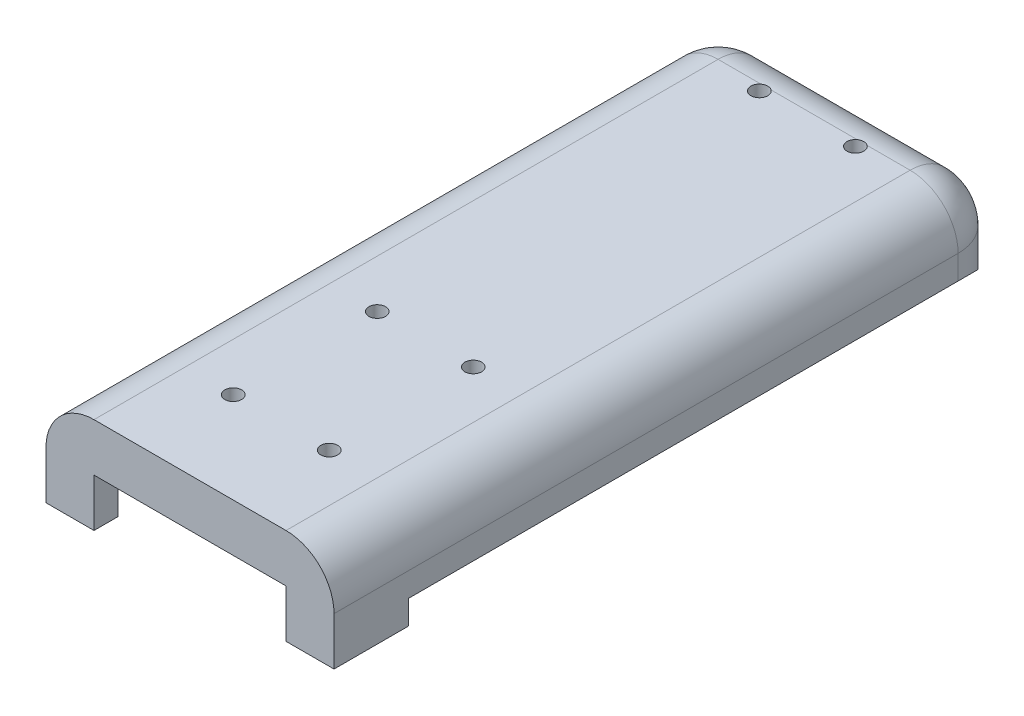
SolidWorks part; units mm, degrees
ref_plane "Front Plane" through (0, 0, 0) normal (0, 0, 1) x (1, 0, 0)
ref_plane "Top Plane" through (0, 0, 0) normal (0, 1, 0) x (1, 0, 0)
ref_plane "Right Plane" through (0, 0, 0) normal (1, 0, 0) x (0, 0, -1)
sketch "Sketch1" plane through (0, 0, 0) normal (0, 0, 1) x (1, 0, 0)
  line L1 (15, -5) -> (45, -5)
  line L3 (10, 0) -> (50, 0)
  line L7 (0, -10) -> (0, -15)
  line L11 (55, -20) -> (60, -15)
  line L12 (0, -15) -> (5, -20)
  line L13 (5, -15) -> (5, -20)
  line L14 (55, -20) -> (55, -15)
  line L16 (60, -15) -> (60, -10)
  arc A0 (10, 0) -> (0, -10) centre (10, -10) ccw
  arc A1 (50, 0) -> (60, -10) centre (50, -10) cw
  arc A2 (55, -15) -> (45, -5) centre (45, -15) ccw
  arc A3 (5, -15) -> (15, -5) centre (15, -15) cw
  point P7 (0, 0)
  point P12 (60, 0)
  point P17 (55, -5)
  point P21 (5, -5)
  dimension "D9" = 10
  dimension "D1" = 60
  dimension "D2" = 5
  dimension "D3" = 15
  dimension "D4" = 15
  dimension "D5" = 5
  dimension "D6" = 5
  dimension "D7" = 15
  dimension "D8" = 15
extrude "Boss-Extrude1" add sketch "Sketch1" along normal blind 124.5
sketch "Sketch2" plane through (0, 0, 124.5) normal (0, 0, 1) x (1, 0, 0)
  line L1 (10, 0) -> (50, 0)
  line L2 (0, -10) -> (0, -20)
  line L3 (0, -20) -> (5, -20)
  line L4 (60, -10) -> (60, -20)
  line L6 (55, -20) -> (60, -20)
  line L9 (0, 0) -> (10, 0) construction
  line L10 (5, -20) -> (55, -20)
  arc A0 (10, 0) -> (0, -10) centre (10, -10) ccw
  arc A1 (50, 0) -> (60, -10) centre (50, -10) cw
  point P15 (0, 0)
  point P20 (60, 0)
  arc M13 (10, 0) -> (0, -10) centre (10, -10) ccw
  line M14 (0, -10) -> (0, -15)
  line M15 (0, -15) -> (5, -20)
  line M16 (5, -20) -> (5, -15)
  arc M17 (5, -15) -> (15, -5) centre (15, -15) cw
  line M18 (15, -5) -> (45, -5)
  arc M19 (45, -5) -> (55, -15) centre (45, -15) cw
  line M20 (55, -15) -> (55, -20)
  line M21 (55, -20) -> (60, -15)
  line M22 (60, -15) -> (60, -10)
  arc M23 (60, -10) -> (50, 0) centre (50, -10) ccw
  line M24 (50, 0) -> (10, 0)
  dimension "D3" = 10
  dimension "D1" = 60
  dimension "D2" = 20
extrude "Boss-Extrude2" add sketch "Sketch2" along normal blind 15.5 contours M24 M13 M14 M15 M16 M17 M18 M19 M20 M21 M22 M23 | L2 L3 M15 | L6 L4 M21 | L6 L4 A1 L1 A0 L2 L3 L10 region at (30, -0.6325, 124.5) region at (1.6667, -18.3333, 124.5) region at (58.3333, -18.3333, 124.5)
sketch "Sketch4" plane through (0, 0, 140) normal (0, 0, 1) x (1, 0, 0)
  line L0 (0, -20) -> (10, -20) construction
  line L1 (0, -20) -> (60, -20) construction
  line L2 (10, -20) -> (10, -10)
  line L3 (10, -10) -> (50, -10)
  line L4 (50, -10) -> (50, -20)
  line L5 (50, -20) -> (10, -20)
  dimension "D1" = 10
  dimension "D2" = 10
  dimension "D3" = 40
extrude "Cut-Extrude3" cut sketch "Sketch4" against normal blind 24.5
sketch "Sketch8" plane through (0, -20, 0) normal (0, -1, 0) x (1, 0, 0)
  line L0 (5, 0) -> (55, 0)
  line L1 (55, 0) -> (55, 5)
  line L2 (55, 124.5) -> (55, 0) construction
  line L3 (55, 5) -> (5, 5)
  line L4 (5, 124.5) -> (5, 0) construction
  line L5 (5, 5) -> (5, 0)
  dimension "D1" = 5
extrude "Boss-Extrude4" add sketch "Sketch8" against normal up to surface (15 mm away) up to face at (30, -5, 62.25)
sketch "Sketch9" plane through (0, -20, 0) normal (0, -1, 0) x (-1, 0, 0)
  line L0 (0, -140) -> (0, -135) construction
  line L1 (0, -140) -> (0, -124.5) construction
  line L2 (0, -135) -> (-4.5, -135) construction
  line L3 (-4.5, -135) -> (-4.5, -129.5)
  line L4 (-4.5, -129.5) -> (-55.5, -129.5)
  line L5 (-55.5, -129.5) -> (-55.5, -135)
  line L6 (-55.5, -135) -> (-4.5, -135)
  line L7 (-60, -140) -> (-60, -124.5) construction
  dimension "D1" = 5
  dimension "D2" = 4.5
  dimension "D3" = 5.5
  dimension "D4" = 4.5
extrude "Cut-Extrude4" cut sketch "Sketch9" against normal offset from surface (15.5 mm away) 4.5 up to face at (30, 0, 70)
sketch "Sketch10" plane through (0, 0, 0) normal (0, 1, 0) x (1, 0, 0)
  line L0 (50, -140) -> (10, -140) construction
  circle A0 centre (20, -11.4) radius 1.75
  circle A1 centre (20, -11.4) radius 6.75
  point P0 (20, -11.4)
  point P1 (40, -11.4)
  point P2 (40, -91)
  point P3 (20, -91)
  point P4 (20, -121)
  point P5 (40, -121)
  dimension "D6" = 3.5
  dimension "D7" = 13.5
  dimension "D1" = 20
  dimension "D2" = 20
  dimension "D3" = 11.4
  dimension "D4" = 19
  dimension "D5" = 30
extrude "Boss-Extrude5" add sketch "Sketch10" against normal blind 19.4 contours A1 | A0
sketch "Sketch11" plane through (0, 0, 0) normal (0, 1, 0) x (1, 0, 0)
  circle A0 centre (20, -11.4) radius 1.75
  dimension "D1" = 3.5
extrude "Cut-Extrude5" cut sketch "Sketch11" against normal through all
pattern_sketch "Sketch-Pattern1" of "Boss-Extrude5", "Cut-Extrude5" driven by "Sketch10"
fillet "Fillet1" radius 10 5 edges at (60, -12.5, 0) (57.0711, -2.9289, 0) (0, -12.5, 0) (2.9289, -2.9289, 0) (30, 0, 0)
